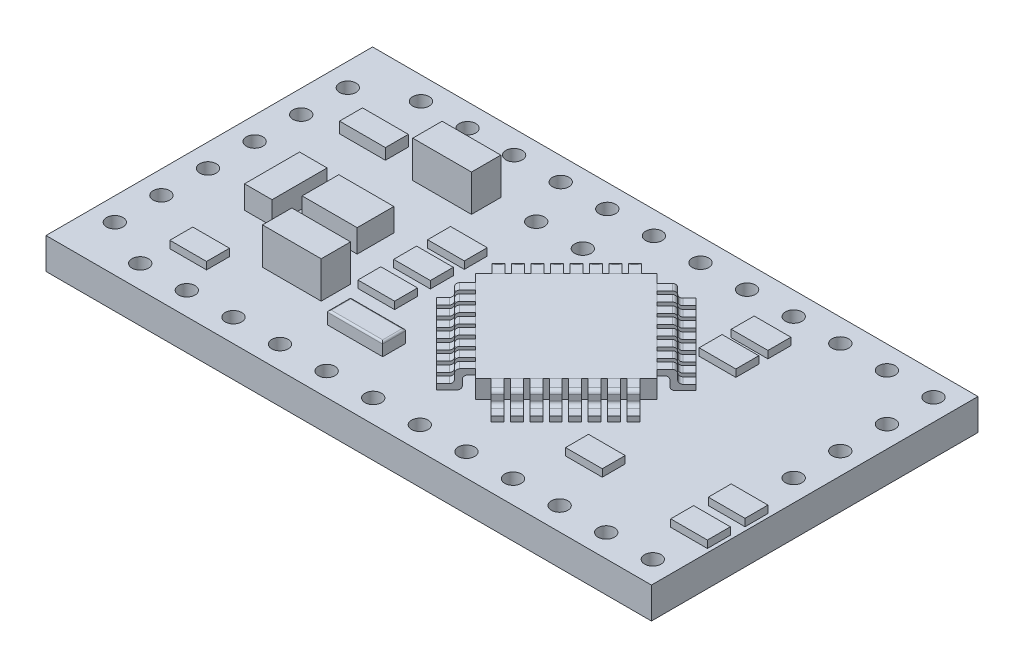
SolidWorks part; units mm, degrees
note: '?' marks a value the reader was unsure of.
ref_plane "Plano frontal" through (0, 0, 0) normal (0, 0, 1) x (1, 0, 0)
ref_plane "Plano superior" through (0, 0, 0) normal (0, 1, 0) x (1, 0, 0)
ref_plane "Plano direito" through (0, 0, 0) normal (1, 0, 0) x (0, 0, -1)
sketch "Esboço1" plane through (0, 0, 0) normal (0, 1, 0) x (1, 0, 0)
  line L1 (-16.5, -8.9) -> (16.5, -8.9)
  line L2 (-16.5, -8.9) -> (-16.5, 8.9)
  line L3 (-16.5, 8.9) -> (16.5, 8.9)
  line L4 (16.5, -8.9) -> (16.5, 8.9)
  line L5 (-16.5, -8.9) -> (16.5, 8.9) construction
  line L6 (-16.5, 8.9) -> (16.5, -8.9) construction
  point P0 (0, 0)
  dimension "D1" = 17.8
  dimension "D2" = 33
extrude "Ressalto-extrusão1" add sketch "Esboço1" along normal mid plane 1.7
sketch "Esboço2" plane through (0, 0.85, 0) normal (0, 1, 0) x (1, 0, 0)
  line L75 (0, 0) -> (2.5277, 0) construction
  circle A0 centre (15.325, 7.65) radius 0.45
  circle A1 centre (12.785, 7.65) radius 0.45
  circle A2 centre (10.245, 7.65) radius 0.45
  circle A3 centre (7.705, 7.65) radius 0.45
  circle A4 centre (5.165, 7.65) radius 0.45
  circle A5 centre (2.625, 7.65) radius 0.45
  circle A6 centre (0.085, 7.65) radius 0.45
  circle A7 centre (-2.455, 7.65) radius 0.45
  circle A8 centre (-4.995, 7.65) radius 0.45
  circle A9 centre (-7.535, 7.65) radius 0.45
  circle A10 centre (-10.075, 7.65) radius 0.45
  circle A11 centre (-12.615, 7.65) radius 0.45
  circle A12 centre (15.325, -7.65) radius 0.45
  circle A13 centre (12.785, -7.65) radius 0.45
  circle A14 centre (10.245, -7.65) radius 0.45
  circle A15 centre (7.705, -7.65) radius 0.45
  circle A16 centre (5.165, -7.65) radius 0.45
  circle A17 centre (2.625, -7.65) radius 0.45
  circle A18 centre (0.085, -7.65) radius 0.45
  circle A19 centre (-2.455, -7.65) radius 0.45
  circle A20 centre (-4.995, -7.65) radius 0.45
  circle A21 centre (-7.535, -7.65) radius 0.45
  circle A22 centre (-10.075, -7.65) radius 0.45
  circle A23 centre (-12.615, -7.65) radius 0.45
  circle A24 centre (-15.25, -6.4) radius 0.45
  circle A25 centre (-15.25, -3.86) radius 0.45
  circle A26 centre (-15.25, -1.32) radius 0.45
  circle A27 centre (-15.25, 1.22) radius 0.45
  circle A28 centre (-15.25, 3.76) radius 0.45
  circle A29 centre (-15.25, 6.3) radius 0.45
  circle A30 centre (-1.25, 5.11) radius 0.45
  circle A31 centre (-3.79, 5.11) radius 0.45
  circle A32 centre (15.325, 5.11) radius 0.45
  circle A33 centre (15.325, 2.57) radius 0.45
  circle A34 centre (15.325, 0.03) radius 0.45
  point P7 (15.325, -7.65)
  point P8 (15.325, 0.03)
  point P9 (12.785, -7.65)
  point P10 (10.245, -7.65)
  point P11 (7.705, -7.65)
  point P12 (5.165, -7.65)
  point P13 (2.625, -7.65)
  point P14 (0.085, -7.65)
  point P15 (-2.455, -7.65)
  point P16 (-4.995, -7.65)
  point P17 (-7.535, -7.65)
  point P18 (-10.075, -7.65)
  point P19 (-12.615, -7.65)
  point P20 (15.325, 2.57)
  point P21 (15.325, 5.11)
  point P22 (15.325, 7.65)
  dimension "D7" = 12
  dimension "D8" = 12
  dimension "D9" = 6
  dimension "D10" = 2
  dimension "D2" = 12
sketch "Esboço15" plane through (0, 0.85, 0) normal (0, 1, 0) x (1, 0, 0)
  line L0 (-16.5, -8.9) -> (16.5, -8.9) construction
  line L1 (-2, 0) -> (2.9497, 4.9497)
  line L2 (-2, 0) -> (2.9497, -4.9497)
  line L3 (2.9497, -4.9497) -> (7.8995, 0)
  line L4 (2.9497, 4.9497) -> (7.8995, 0)
  line L5 (16.5, -8.9) -> (16.5, 8.9) construction
  line L6 (7.8995, 0) -> (16.5, 0) construction
  dimension "D1" = 45
  dimension "D2" = 7
  dimension "D3" = 18.5
extrude "Ressalto-extrusão6" add sketch "Esboço15" along normal blind 1 separate body
ref_plane "Plano1" through (3.5255, 0, 3.5255) normal (0.7071, 0, 0.7071) x (0.7071, 0, -0.7071)
sketch "Esboço18" plane through (3.5255, 0, 3.5255) normal (0.7071, 0, 0.7071) x (0.7071, 0, -0.7071)
  line L0 (5.5858, 1.85) -> (6.1858, 1.85)
  line L1 (6.3858, 1.65) -> (6.3858, 1.35)
  line L2 (6.5858, 1.15) -> (7.0858, 1.15)
  line L3 (7.0858, 1.15) -> (7.0858, 0.85)
  line L4 (7.0858, 0.85) -> (6.2858, 0.85)
  line L5 (6.0858, 1.05) -> (6.0858, 1.35)
  line L6 (5.8858, 1.55) -> (5.5858, 1.55)
  line L7 (5.5858, 1.55) -> (5.5858, 1.85)
  line L8 (-1.4142, 0.85) -> (5.5858, 0.85) construction
  arc A0 (6.3858, 1.35) -> (6.5858, 1.15) centre (6.5858, 1.35) ccw
  arc A1 (6.2858, 0.85) -> (6.0858, 1.05) centre (6.2858, 1.05) cw
  arc A2 (6.1858, 1.85) -> (6.3858, 1.65) centre (6.1858, 1.65) cw
  arc A3 (6.0858, 1.35) -> (5.8858, 1.55) centre (5.8858, 1.35) ccw
  point P15 (6.0858, 0.85)
  dimension "D5" = 0.2
  dimension "D1" = 0.3
  dimension "D2" = 0.3
  dimension "D3" = 0.3
  dimension "D4" = 1.5
  dimension "D6" = 0.8
extrude "Ressalto-extrusão9" add sketch "Esboço18" against normal blind 0.5 separate body contours L5 A3 L6 L7 L0 A2 L1 A0 L2 L3 L4 A1
pattern_linear "Padrão linear3" count 8 spacing 0.75 along (-0.7071, 0, -0.7071) of "Ressalto-extrusão9"
pattern_linear "Padrão linear4" count 8 spacing 0.75 along (-0.7071, 0, -0.7071) of bodies 220
sketch "Esboço19" plane through (0, 1.85, 0) normal (0, 1, 0) x (1, 0, 0)
  line L0 (-2, 0) -> (7.8995, 0) construction
  line L1 (-2, 0) -> (2.9497, -4.9497) construction
  line L2 (2.9497, 4.9497) -> (-2, 0) construction
  point P7 (2.9497, 0)
ref_axis "Eixo1" through (2.9497, 1.85, 0) along (0, 1, 0)?
pattern_circular "PadrãoCircular1" count 4 over 360 about axis through (2.9497, 0, 0) along (0, 1, 0) of bodies 227 226 225 224 223 222 221 220
sketch "Esboço27" plane through (0, 0.85, 0) normal (0, 1, 0) x (1, 0, 0)
  line L0 (-16.5, -8.9) -> (16.5, -8.9) construction
  line L1 (14.3, -2.35) -> (16.3, -2.35)
  line L2 (14.3, -2.35) -> (14.3, -3.6)
  line L3 (14.3, -3.6) -> (16.3, -3.6)
  line L4 (16.3, -2.35) -> (16.3, -3.6)
  line L5 (14.3, -4.4) -> (16.3, -4.4)
  line L6 (14.3, -4.4) -> (14.3, -5.65)
  line L7 (14.3, -5.65) -> (16.3, -5.65)
  line L8 (16.3, -4.4) -> (16.3, -5.65)
  line L9 (8.07, -3.9) -> (10.07, -3.9)
  line L10 (8.07, -3.9) -> (8.07, -5.15)
  line L11 (8.07, -5.15) -> (10.07, -5.15)
  line L12 (10.07, -3.9) -> (10.07, -5.15)
  line L13 (7, 6.2) -> (9, 6.2)
  line L14 (7, 6.2) -> (7, 4.95)
  line L15 (7, 4.95) -> (9, 4.95)
  line L16 (9, 6.2) -> (9, 4.95)
  line L17 (7, 4.45) -> (9, 4.45)
  line L18 (7, 4.45) -> (7, 3.2)
  line L19 (7, 3.2) -> (9, 3.2)
  line L20 (9, 4.45) -> (9, 3.2)
  line L21 (-5.5, 2.15) -> (-3.5, 2.15)
  line L22 (-5.5, 2.15) -> (-5.5, 0.9)
  line L23 (-5.5, 0.9) -> (-3.5, 0.9)
  line L24 (-3.5, 2.15) -> (-3.5, 0.9)
  line L25 (-5.5, 0.3) -> (-3.5, 0.3)
  line L26 (-5.5, 0.3) -> (-5.5, -0.95)
  line L27 (-5.5, -0.95) -> (-3.5, -0.95)
  line L28 (-3.5, 0.3) -> (-3.5, -0.95)
  line L29 (-5.5, -1.65) -> (-3.5, -1.65)
  line L30 (-5.5, -1.65) -> (-5.5, -2.9)
  line L31 (-5.5, -2.9) -> (-3.5, -2.9)
  line L32 (-3.5, -1.65) -> (-3.5, -2.9)
  line L33 (-12.5, -4.9) -> (-10.5, -4.9)
  line L34 (-12.5, -4.9) -> (-12.5, -6.15)
  line L35 (-12.5, -6.15) -> (-10.5, -6.15)
  line L36 (-10.5, -4.9) -> (-10.5, -6.15)
  line L37 (16.5, -8.9) -> (16.5, 8.9) construction
  line L38 (-16.5, 8.9) -> (-16.5, -8.9) construction
  line L39 (16.5, 8.9) -> (-16.5, 8.9) construction
  dimension "D1" = 2
  dimension "D2" = 1.25
  dimension "D3" = 4.5
  dimension "D4" = 0.8
  dimension "D5" = 0.2
  dimension "D6" = 4.23
  dimension "D7" = 5
  dimension "D8" = 4
  dimension "D9" = 6
  dimension "D10" = 0.6
  dimension "D11" = 0.7
  dimension "D12" = 9.2
  dimension "D13" = 13
  dimension "D14" = 0.5
  dimension "D15" = 5.7
  dimension "D16" = 9.5
extrude "Ressalto-extrusão10" add sketch "Esboço27" along normal blind 0.4 separate body contours L24 L21 L22 L23 | L28 L25 L26 L27 | L32 L29 L30 L31 | L12 L9 L10 L11 | L4 L1 L2 L3 | L8 L5 L6 L7 | L20 L17 L18 L19 | L36 L33 L34 L35 | L15 L16 L13 L14
sketch "Esboço28" plane through (0, 0.85, 0) normal (0, 1, 0) x (1, 0, 0)
  line L0 (-16.5, 8.9) -> (-16.5, -8.9) construction
  line L1 (-9.1, 5.29) -> (-5.9, 5.29)
  line L2 (-9.1, 5.29) -> (-9.1, 3.69)
  line L3 (-9.1, 3.69) -> (-5.9, 3.69)
  line L4 (-5.9, 5.29) -> (-5.9, 3.69)
  line L5 (-9.1, -2.9) -> (-5.9, -2.9)
  line L6 (-9.1, -2.9) -> (-9.1, -4.5)
  line L7 (-9.1, -4.5) -> (-5.9, -4.5)
  line L8 (-5.9, -2.9) -> (-5.9, -4.5)
  line L9 (16.5, 8.9) -> (-16.5, 8.9) construction
  line L10 (-16.5, -8.9) -> (16.5, -8.9) construction
  dimension "D1" = 1.6
  dimension "D2" = 3.2
  dimension "D3" = 10.6
  dimension "D4" = 5.21
  dimension "D5" = 6
extrude "Ressalto-extrusão11" add sketch "Esboço28" along normal blind 2 separate body
sketch "Esboço29" plane through (0, 0.85, 0) normal (0, 1, 0) x (1, 0, 0)
  line L0 (-16.5, 8.9) -> (-16.5, -8.9) construction
  line L1 (-12.28, 0.7) -> (-10.78, 0.7)
  line L2 (-12.28, 0.7) -> (-12.28, -2.3)
  line L3 (-12.28, -2.3) -> (-10.78, -2.3)
  line L4 (-10.78, 0.7) -> (-10.78, -2.3)
  line L5 (-10.14, 0.7) -> (-7.14, 0.7)
  line L6 (-10.14, 0.7) -> (-10.14, -1.3)
  line L7 (-10.14, -1.3) -> (-7.14, -1.3)
  line L8 (-7.14, 0.7) -> (-7.14, -1.3)
  line L9 (16.5, 8.9) -> (-16.5, 8.9) construction
  dimension "D1" = 3
  dimension "D2" = 2
  dimension "D3" = 3
  dimension "D4" = 1.5
  dimension "D5" = 0.64
  dimension "D6" = 9.36
  dimension "D7" = 10.2
extrude "Ressalto-extrusão12" add sketch "Esboço29" along normal blind 1.25 separate body
sketch "Esboço31" plane through (0, 0.85, 0) normal (0, 1, 0) x (1, 0, 0)
  line L0 (-16.5, -8.9) -> (16.5, -8.9) construction
  line L1 (-4.6, -4.2) -> (-1.6, -4.2)
  line L2 (-4.6, -4.2) -> (-4.6, -5.45)
  line L3 (-4.6, -5.45) -> (-1.6, -5.45)
  line L4 (-1.6, -4.2) -> (-1.6, -5.45)
  line L5 (-5.9, -4.5) -> (-5.9, -2.9) construction
  dimension "D1" = 3
  dimension "D2" = 1.25
  dimension "D3" = 4.7
  dimension "D4" = 1.3
extrude "Ressalto-extrusão14" add sketch "Esboço31" along normal blind 0.7 separate body
sketch "Esboço32" plane through (0, 0.85, 0) normal (0, 1, 0) x (1, 0, 0)
  line L0 (16.5, 8.9) -> (-16.5, 8.9) construction
  line L1 (-13.3, 5.15) -> (-10.8, 5.15)
  line L2 (-13.3, 5.15) -> (-13.3, 3.9)
  line L3 (-13.3, 3.9) -> (-10.8, 3.9)
  line L4 (-10.8, 5.15) -> (-10.8, 3.9)
  line L5 (-16.5, 8.9) -> (-16.5, -8.9) construction
  dimension "D1" = 2.5
  dimension "D2" = 1.25
  dimension "D3" = 5
  dimension "D4" = 5.7
extrude "Ressalto-extrusão15" add sketch "Esboço32" along normal blind 0.6 separate body
fillet "Filete20" radius 0.1 4 edges at (-3.1, 1.55, 4.2) (-1.6, 1.55, 4.825) (-3.1, 1.55, 5.45) (-4.6, 1.55, 4.825)
extrude "Вырез-Вытянуть1" cut sketch "Esboço2" against normal through all
sketch "Эскиз1" plane through (0, 0.85, 0) normal (0, 1, 0) x (1, 0, 0)
  point P0 (15.325, -7.65)
  point P1 (15.325, 0.03)
  point P3 (12.785, -7.65)
  point P4 (10.245, -7.65)
  point P5 (7.705, -7.65)
  point P6 (5.165, -7.65)
  point P7 (2.625, -7.65)
  point P8 (0.085, -7.65)
  point P9 (-2.455, -7.65)
  point P10 (-4.995, -7.65)
  point P11 (-7.535, -7.65)
  point P12 (-10.075, -7.65)
  point P13 (-12.615, -7.65)
  point P14 (15.325, 2.57)
  point P16 (15.325, 5.11)
  point P18 (15.325, 7.65)
  point P20 (12.785, 7.65)
  point P22 (10.245, 7.65)
  point P24 (7.705, 7.65)
  point P26 (2.625, 7.65)
  point P28 (0.085, 7.65)
  point P30 (-2.455, 7.65)
  dimension "D1" = 12
